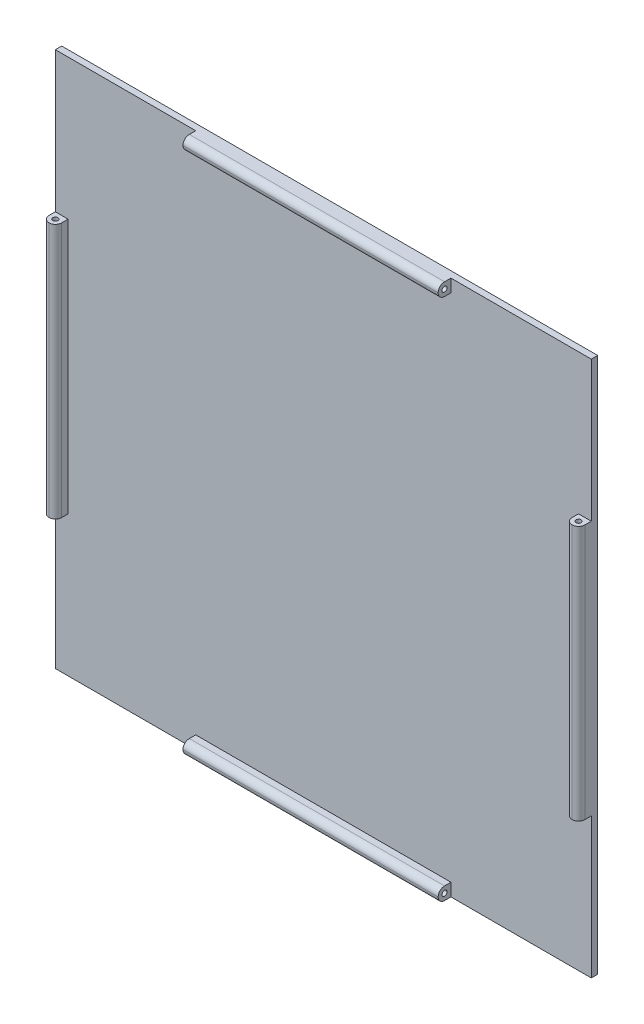
SolidWorks part; units mm, degrees
ref_plane "前视基准面" through (0, 0, 0) normal (0, 0, 1) x (1, 0, 0)
ref_plane "上视基准面" through (0, 0, 0) normal (0, 1, 0) x (1, 0, 0)
ref_plane "右视基准面" through (0, 0, 0) normal (1, 0, 0) x (0, 0, -1)
sketch "草图1" plane through (0, 0, 0) normal (0, 0, 1) x (1, 0, 0)
  line L1 (210, -210) -> (-210, -210)
  line L2 (210, -210) -> (210, 210)
  line L3 (210, 210) -> (-210, 210)
  line L4 (-210, -210) -> (-210, 210)
  line L5 (210, -210) -> (-210, 210) construction
  line L6 (210, 210) -> (-210, -210) construction
  point P0 (0, 0)
  dimension "D1" = 420
  dimension "D2" = 420
extrude "凸台-拉伸1" add sketch "草图1" along normal blind 5
sketch "草图3" plane through (0, 0, 0) normal (0, 0, -1) x (-1, 0, 0)
  line L0 (-210, 0) -> (210, 0) construction
  line L1 (-155, -200) -> (-105, -200)
  line L2 (-155, -200) -> (-155, -210)
  line L3 (-155, -210) -> (-105, -210)
  line L4 (210, -210) -> (210, 210)
  line L5 (210, 210) -> (-210, 210)
  line L6 (-210, 210) -> (-210, -210)
  line L7 (-210, -210) -> (210, -210)
  line L8 (210, -210) -> (210, 210)
  line L9 (210, 210) -> (-210, 210)
  line L10 (-210, 210) -> (-210, -210)
  line L11 (-210, -210) -> (210, -210)
  line L12 (-105, -200) -> (-105, -210)
  line L13 (105, -200) -> (155, -200)
  line L14 (105, -200) -> (105, -210)
  line L15 (105, -210) -> (155, -210)
  line L16 (155, -200) -> (155, -210)
  line L17 (0, 210) -> (0, -210) construction
  line L19 (-155, 210) -> (-105, 210)
  line L20 (-155, 210) -> (-155, 200)
  line L21 (-155, 200) -> (-105, 200)
  line L22 (-105, 210) -> (-105, 200)
  line L23 (105, 210) -> (155, 210)
  line L24 (105, 210) -> (105, 200)
  line L25 (105, 200) -> (155, 200)
  line L26 (155, 210) -> (155, 200)
  line L27 (-210, 155) -> (-200, 155)
  line L28 (-210, 155) -> (-210, 105)
  line L29 (-210, 105) -> (-200, 105)
  line L30 (-200, 155) -> (-200, 105)
  line L31 (-210, -105) -> (-200, -105)
  line L32 (-210, -105) -> (-210, -155)
  line L33 (-210, -155) -> (-200, -155)
  line L34 (-200, -105) -> (-200, -155)
  line L35 (210, 155) -> (200, 155)
  line L36 (210, 155) -> (210, 105)
  line L37 (210, 105) -> (200, 105)
  line L38 (200, 155) -> (200, 105)
  line L39 (210, -105) -> (200, -105)
  line L40 (210, -105) -> (210, -155)
  line L41 (210, -155) -> (200, -155)
  line L42 (200, -105) -> (200, -155)
  point P12 (-155, -205)
  line M14 (-210, -210) -> (210, -210)
  dimension "D2" = 50
  dimension "D3" = 10
  dimension "D4" = 50
  dimension "D5" = 10
  dimension "D6" = 55
  dimension "D7" = 55
  dimension "D8" = 55
  dimension "D9" = 50
  dimension "D10" = 10
  dimension "D11" = 55
  dimension "D12" = 50
  dimension "D13" = 10
  dimension "D1" = 0
extrude "凸台-拉伸2" add sketch "草图3" along normal blind 10 contours L12 L1 L2 M14 | L34 L31 L10 L33 | L30 L27 L10 L29 | L22 L9 L20 L21 | L35 L38 L37 L8 | L26 L9 L24 L25 | L39 L42 L41 L8 | L16 L13 L14 L11 region at (130, -205, 0) region at (-130, -205, 0) region at (205, -130, 0) region at (205, 130, 0) region at (-205, -130, 0) region at (-205, 130, 0) region at (130, 205, 0) region at (-130, 205, 0)
sketch "草图4" plane through (0, 0, 5) normal (0, 0, 1) x (1, 0, 0)
  line L0 (-210, -210) -> (210, -210) construction
  line L1 (100, -210) -> (-100, -210)
  line L2 (100, -210) -> (100, -200)
  line L3 (100, -200) -> (-100, -200)
  line L4 (-100, -210) -> (-100, -200)
  line L5 (210, -210) -> (210, 210) construction
  line L6 (210, -100) -> (200, -100)
  line L7 (210, -100) -> (210, 100)
  line L8 (210, 100) -> (200, 100)
  line L9 (200, -100) -> (200, 100)
  line L10 (210, 210) -> (-210, 210) construction
  line L11 (100, 200) -> (-100, 200)
  line L12 (100, 200) -> (100, 210)
  line L13 (100, 210) -> (-100, 210)
  line L14 (-100, 200) -> (-100, 210)
  line L15 (-210, 210) -> (-210, -210) construction
  line L16 (-200, -100) -> (-210, -100)
  line L17 (-200, -100) -> (-200, 100)
  line L18 (-200, 100) -> (-210, 100)
  line L19 (-210, -100) -> (-210, 100)
  dimension "D1" = 10
  dimension "D2" = 10
  dimension "D3" = 10
  dimension "D4" = 10
  dimension "D5" = 200
  dimension "D6" = 110
  dimension "D7" = 110
  dimension "D8" = 200
extrude "凸台-拉伸3" add sketch "草图4" along normal blind 10 contours L7 L6 L9 L8 | L2 L1 L4 L3 | L17 L16 L19 L18 | L12 L11 L14 L13
fillet "圆角1" radius 5 24 edges at (-210, 0, 15) (-200, 0, 15) (0, -210, 15) (0, -200, 15) (0, 200, 15) (0, 210, 15) (200, 0, 15) (210, 0, 15) (200, -130, -10) (210, -130, -10) (130, 210, -10) (130, 200, -10) (200, 130, -10) (210, 130, -10) (-130, -210, -10) (-130, -200, -10) (-130, 210, -10) (-130, 200, -10) (-210, 130, -10) (-200, 130, -10) (-210, -130, -10) (-200, -130, -10) (130, -210, -10) (130, -200, -10)
sketch "草图5" plane through (0, 155, 0) normal (0, 1, 0) x (1, 0, 0)
  circle A0 centre (205, 5) radius 2
  dimension "D1" = 4
extrude "切除-拉伸1" cut sketch "草图5" against normal through all
sketch "草图6" plane through (0, 100, 0) normal (0, 1, 0) x (1, 0, 0)
  line L0 (200, -10) -> (210, -10) construction
  circle A0 centre (205, -10) radius 2
  dimension "D1" = 4
extrude "切除-拉伸2" cut sketch "草图6" against normal through all
sketch "草图7" plane through (155, 0, 0) normal (1, 0, 0) x (0, 0, -1)
  circle A2 centre (5, -205) radius 2
  dimension "D1" = 4
extrude "切除-拉伸3" cut sketch "草图7" against normal through all both and the other way through all
sketch "草图8" plane through (100, 0, 0) normal (1, 0, 0) x (0, 0, -1)
  circle A0 centre (-10, -205) radius 2
  dimension "D1" = 4
extrude "切除-拉伸4" cut sketch "草图8" against normal through all contours A0
sketch "草图9" plane through (0, -155, 0) normal (0, -1, 0) x (1, 0, 0)
  circle A0 centre (-205, -5) radius 2
  dimension "D1" = 4
extrude "切除-拉伸5" cut sketch "草图9" against normal through all both and the other way through all
sketch "草图10" plane through (0, -100, 0) normal (0, -1, 0) x (1, 0, 0)
  circle A0 centre (-205, 10) radius 2
  dimension "D1" = 4
extrude "切除-拉伸6" cut sketch "草图10" against normal through all contours A0
sketch "草图11" plane through (-155, 0, 0) normal (-1, 0, 0) x (0, 0, 1)
  circle A0 centre (-5, 205) radius 2
  dimension "D1" = 4
extrude "切除-拉伸7" cut sketch "草图11" against normal through all both and the other way through all
sketch "草图12" plane through (-100, 0, 0) normal (-1, 0, 0) x (0, 0, 1)
  circle A0 centre (10, 205) radius 2
  dimension "D1" = 4
extrude "切除-拉伸8" cut sketch "草图12" against normal through all
scale "缩放比例1" scale about origin uniform scaling yes scale factor 0.5
sketch "草图13" plane through (0, 0, 0) normal (0, 0, -1) x (-1, 0, 0)
  line L1 (-105, 105) -> (105, 105)
  line L2 (-105, 105) -> (-105, -105)
  line L3 (-105, -105) -> (105, -105)
  line L4 (105, 105) -> (105, -105)
  dimension "D1" = 210
extrude "切除-拉伸9" cut sketch "草图13" along normal blind 90
sketch "草图14" plane through (0, 0, 0) normal (0, 0, -1) x (-1, 0, 0)
  line L2 (-50, 50) -> (50, 50)
  line L3 (-50, 50) -> (-50, -50)
  line L4 (-50, -50) -> (50, -50)
  line L5 (50, 50) -> (50, -50)
  line L6 (0, -50) -> (0, 50) construction
  line L7 (-50, 0) -> (50, 0) construction
  point P4 (0, 0)
  dimension "D1" = 100
extrude "凸台-拉伸4" add sketch "草图14" along normal blind 12 contours L3 L2 L5 L4
fillet "圆角2" radius 12 4 edges at (50, 0, 0) (0, -50, 0) (-50, 0, 0) (0, 50, 0)
sketch "草图15" plane through (0, 0, -12) normal (0, 0, -1) x (-1, 0, 0)
  circle A0 centre (-35, 35) radius 2
  circle A1 centre (35, 35) radius 2
  circle A2 centre (-35, -35) radius 2
  circle A3 centre (35, -35) radius 2
extrude "切除-拉伸10" cut sketch "草图15" against normal blind 5
